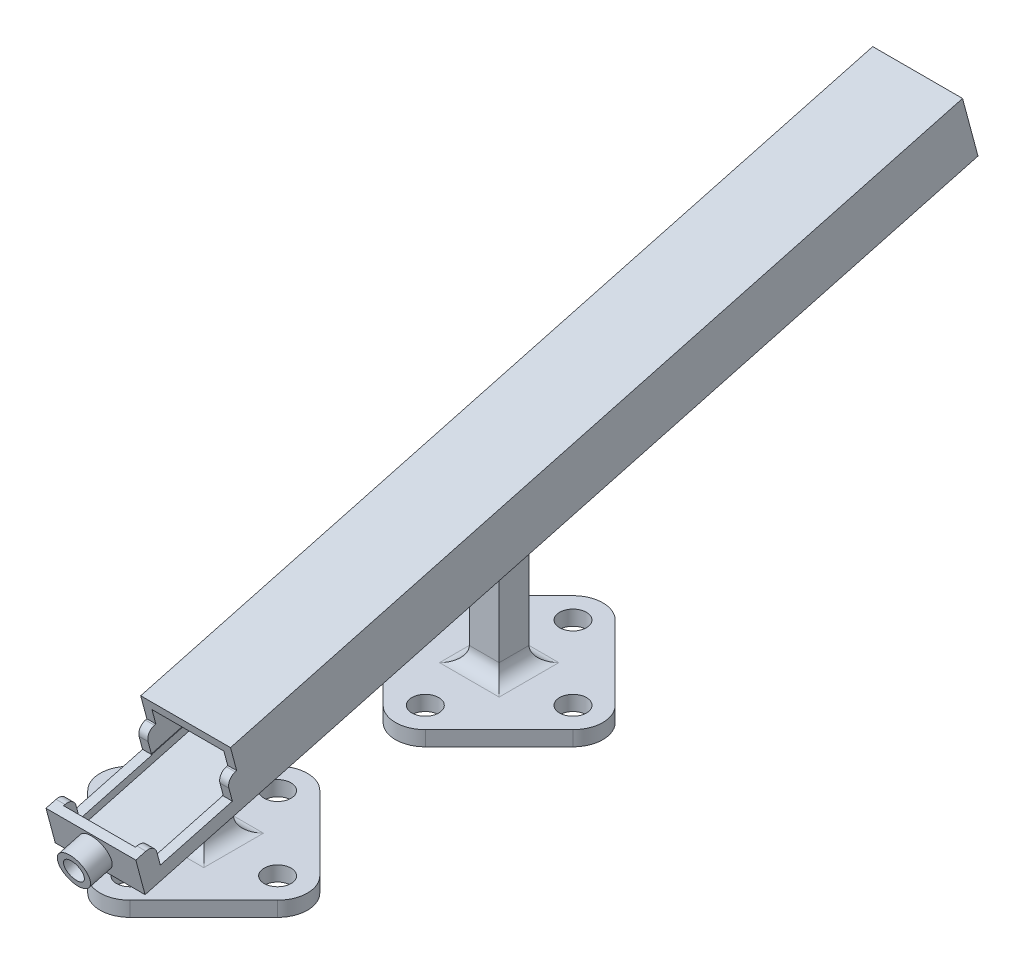
SolidWorks part; units mm, degrees
ref_plane "Front" through (0, 0, 0) normal (0, 0, 1) x (1, 0, 0)
ref_plane "Top" through (0, 0, 0) normal (0, 1, 0) x (1, 0, 0)
ref_plane "Right" through (0, 0, 0) normal (1, 0, 0) x (0, 0, -1)
ref_axis "Axis1" through (0, 55, 0) along (0, -1, 0)
ref_axis "Axis2" through (88.99, 0, 0) along (-1, 0, 0)
ref_axis "Axis3" through (0, 0, 55) along (0, 0, -1)
sketch "Sketch1" plane through (0, 0, 0) normal (0, 1, 0) x (1, 0, 0)
  line L0 (-24.75, 0) -> (0, 24.75) construction
  line L9 (-24.75, 0) -> (0, -24.75) construction
  line L11 (0, 24.75) -> (24.75, 0) construction
  line L12 (0, -24.75) -> (24.75, 0) construction
  line L13 (-24.75, 0) -> (24.75, 0) construction
  line L14 (0, 24.75) -> (0, -24.75) construction
  line L15 (-31.8211, 7.0711) -> (-7.0711, 31.8211)
  line L16 (7.0711, 31.8211) -> (31.8211, 7.0711)
  line L17 (7.0711, -31.8211) -> (31.8211, -7.0711)
  line L18 (-31.8211, -7.0711) -> (-7.0711, -31.8211)
  line L19 (0, -38.8921) -> (38.8921, 0) construction
  line L20 (-38.8921, 0) -> (0, -38.8921) construction
  line L21 (0, 38.8921) -> (38.8921, 0) construction
  line L22 (-38.8921, 0) -> (0, 38.8921) construction
  arc A4 (7.0711, -31.8211) -> (-7.0711, -31.8211) centre (0, -24.75) cw
  arc A5 (31.8211, 7.0711) -> (31.8211, -7.0711) centre (24.75, 0) cw
  arc A6 (-7.0711, 31.8211) -> (7.0711, 31.8211) centre (0, 24.75) cw
  arc A7 (-31.8211, 7.0711) -> (-31.8211, -7.0711) centre (-24.75, 0) ccw
  circle A8 centre (0, 24.75) radius 4.5
  circle A9 centre (24.75, 0) radius 4.5
  circle A10 centre (0, -24.75) radius 4.5
  circle A11 centre (-24.75, 0) radius 4.5
  point P1 (0, 0)
  dimension "D3" = 10
  dimension "D4" = 9
  dimension "D1" = 49.5
  dimension "D2" = 10
extrude "Boss-Extrude1" add sketch "Sketch1" along normal mid plane 5
ref_plane "Plane1" through (0, 0, 49.5) normal (0, 0, 1) x (1, 0, 0)
mirror "Mirror3" about plane through (0, 0, 49.5) normal (0, 0, 1) of bodies 101
sketch "Sketch2" plane through (0, 0, 0) normal (1, 0, 0) x (0, 0, -1)
  line L0 (-106.0711, 2.5) -> (-130.8211, 2.5) construction
  line L1 (-104, 2.5) -> (-94, 2.5)
  line L2 (-104, 2.5) -> (-104, 47.5)
  line L3 (-104, 47.5) -> (-94, 47.5)
  line L4 (-94, 2.5) -> (-94, 47.5)
  line L5 (-106.0711, -2.5) -> (-91.9289, -2.5) construction
  line L6 (-67.1789, -2.5) -> (-91.9289, -2.5) construction
  point P8 (-99, -2.5)
  point P9 (-99, 47.5)
  dimension "D1" = 10
  dimension "D2" = 50
extrude "Boss-Extrude2" add sketch "Sketch2" along normal mid plane 10 separate body
mirror "Mirror5" about plane through (0, 0, 49.5) normal (0, 0, 1) of bodies 103
sketch "Sketch3" plane through (0, 0, 0) normal (1, 0, 0) x (0, 0, -1)
  line L0 (-104, 17.5) -> (5, 46.7065)
  line L1 (-67.1789, -2.5) -> (-91.9289, -2.5) construction
  line L2 (-104, 47.5) -> (-104, 2.5) construction
  line L3 (-106.0711, 2.5) -> (-130.8211, 2.5) construction
  line L4 (5, 47.5) -> (5, 2.5) construction
  point P6 (-104, 17.5)
  dimension "D1" = 15
  dimension "D2" = 15
extrude "Cut-Extrude1" cut sketch "Sketch3" against normal through all both and the other way through all
sketch "Sketch4" plane through (0, 0, 0) normal (1, 0, 0) x (0, 0, -1)
  line L0 (-130.8211, 10.3133) -> (14.0678, 49.1362)
  line L1 (-130.8211, 10.3133) -> (-131.3387, 12.2452)
  line L2 (14.0678, 49.1362) -> (13.5502, 51.068)
  line L3 (-131.3387, 12.2452) -> (13.5502, 51.068)
  line L6 (-104, 17.5) -> (-94, 20.1795) construction
  dimension "D1" = 2
  dimension "D2" = 150
extrude "Boss-Extrude3" add sketch "Sketch4" along normal mid plane 24.1 separate body
combine bodies "Combine1" operation type add bodies to combine 102 106
combine bodies "Combine2" operation type add bodies to combine 107 101
fillet "Fillet1" radius 5 4 edges at (0, 2.5, 94) (-5, 2.5, 99) (0, 2.5, 104) (5, 2.5, 99)
fillet "Fillet2" radius 5 4 edges at (0, 2.5, 5) (0, 2.5, -5) (-5, 2.5, 0) (5, 2.5, 0)
sketch "Sketch5" plane through (0, 44.2596, 11.8593) normal (0, 0.9659, 0.2588) x (1, 0, 0)
  line L0 (12.05, -111.6442) -> (0, -111.6442) construction
  line L1 (12.05, 26.3058) -> (12.05, -123.6942) construction
  line L2 (0, -111.6442) -> (0, -123.6942) construction
  line L3 (12.05, -123.6942) -> (-12.05, -123.6942) construction
  line L4 (-11.83, -111.6442) -> (-12.05, -123.6942)
  line L5 (-12.05, -123.6942) -> (0, -123.6942)
  line L6 (0, -123.6942) -> (12.05, -123.6942)
  line L7 (12.05, -123.6942) -> (12.05, -111.6442)
  circle A0 centre (0, -111.6442) radius 8.73 construction
  circle A1 centre (0, -111.6442) radius 8.83
  circle A2 centre (0, -111.6442) radius 11.83
  dimension "D1" = 17.46
  dimension "D2" = 0.1
  dimension "D3" = 3
sketch "Sketch6" plane through (0, 44.2596, 11.8593) normal (0, 0.9659, 0.2588) x (1, 0, 0)
  line L4 (-12.05, 26.3058) -> (-12.05, -123.6942)
  line L5 (-12.05, -123.6942) -> (12.05, -123.6942)
  line L6 (12.05, -123.6942) -> (12.05, 26.3058)
  line L7 (12.05, 26.3058) -> (-12.05, 26.3058)
  line L8 (-12.05, 26.3058) -> (-12.05, -123.6942)
  line L9 (-12.05, -123.6942) -> (12.05, -123.6942)
  line L10 (12.05, -123.6942) -> (12.05, 26.3058)
  line L11 (12.05, 26.3058) -> (-12.05, 26.3058)
  line L16 (-15.05, 29.3058) -> (-15.05, -126.6942)
  line L17 (-15.05, -126.6942) -> (15.05, -126.6942)
  line L18 (15.05, -126.6942) -> (15.05, 29.3058)
  line L19 (15.05, 29.3058) -> (-15.05, 29.3058)
  line L20 (-15.05, 29.3058) -> (-15.05, -126.6942)
  line L21 (-15.05, -126.6942) -> (15.05, -126.6942)
  line L22 (15.05, -126.6942) -> (15.05, 29.3058)
  line L23 (15.05, 29.3058) -> (-15.05, 29.3058)
  dimension "D1" = 0
  dimension "D2" = 3
extrude "Boss-Extrude4" add sketch "Sketch6" against normal up to vertex (2 mm away) and the other way blind 10 up to point (12.05, 49.1362, -14.0678)
sketch "Sketch7" plane through (0, 53.9188, 14.4475) normal (0, 0.9659, 0.2588) x (1, 0, 0)
  line L0 (12.05, 26.3058) -> (12.05, -123.6942) construction
  line L1 (12.05, 26.3058) -> (12.05, -91.6942)
  line L3 (-12.05, 26.3058) -> (-12.05, -123.6942) construction
  line L4 (15.05, 29.3058) -> (-15.05, 29.3058)
  line L5 (-15.05, 29.3058) -> (-15.05, -126.6942)
  line L6 (-15.05, -126.6942) -> (15.05, -126.6942)
  line L7 (15.05, -126.6942) -> (15.05, 29.3058)
  line L8 (15.05, 29.3058) -> (-15.05, 29.3058)
  line L9 (-15.05, 29.3058) -> (-15.05, -91.6942)
  line L11 (15.05, -91.6942) -> (15.05, 29.3058)
  line L12 (12.05, 26.3058) -> (-12.05, 26.3058) construction
  line L14 (-12.05, 26.3058) -> (-12.05, -91.6942)
  line L15 (12.05, 26.3058) -> (-12.05, 26.3058)
  line L16 (15.05, -91.6942) -> (12.05, -91.6942)
  line L17 (-12.05, -91.6942) -> (-15.05, -91.6942)
  line L18 (-15.05, -126.6942) -> (15.05, -126.6942) construction
  dimension "D2" = 35
  dimension "D1" = 0
extrude "Boss-Extrude5" add sketch "Sketch7" along normal blind 5
sketch "Sketch8" plane through (0, 58.7485, 15.7416) normal (0, 0.9659, 0.2588) x (1, 0, 0)
  line L0 (-15.05, 29.3058) -> (-15.05, -91.6942) construction
  line L1 (-15.05, -91.6942) -> (15.05, -91.6942)
  line L2 (-15.05, -91.6942) -> (-15.05, 29.3058)
  line L3 (-15.05, 29.3058) -> (15.05, 29.3058)
  line L4 (15.05, -91.6942) -> (15.05, 29.3058)
extrude "Boss-Extrude6" add sketch "Sketch8" along normal blind 3
sketch "Sketch10" plane through (0, 6.8085, -25.4095) normal (0, -0.2588, 0.9659) x (1, 0, 0)
  line L4 (-12.05, 45.8209) -> (12.05, 45.8209)
  line L5 (12.05, 45.8209) -> (12.05, 60.8209)
  line L6 (12.05, 60.8209) -> (-12.05, 60.8209)
  line L7 (-12.05, 60.8209) -> (-12.05, 45.8209)
  line L8 (-12.05, 45.8209) -> (12.05, 45.8209)
  line L9 (12.05, 45.8209) -> (12.05, 60.8209)
  line L10 (12.05, 60.8209) -> (-12.05, 60.8209)
  line L11 (-12.05, 60.8209) -> (-12.05, 45.8209)
  dimension "D1" = 0
extrude "Cut-Extrude2" cut sketch "Sketch10" against normal up to next
sketch "Sketch11" plane through (0, 7.5849, -28.3073) normal (0, 0.2588, -0.9659) x (-1, 0, 0)
  line L0 (-12.05, 45.8209) -> (-11.85, 45.8209)
  line L1 (-12.05, 45.8209) -> (12.05, 45.8209) construction
  line L2 (-11.85, 45.8209) -> (-11.85, 48.5209)
  line L3 (-11.85, 48.5209) -> (-12.05, 48.5209)
  line L4 (-12.05, 60.8209) -> (-12.05, 45.8209) construction
  line L5 (-12.05, 48.5209) -> (-12.05, 45.8209)
  line L6 (0, 43.8209) -> (0, 45.8209) construction
  line L7 (-15.05, 43.8209) -> (15.05, 43.8209) construction
  line L8 (12.05, 48.5209) -> (12.05, 45.8209)
  line L9 (11.85, 48.5209) -> (12.05, 48.5209)
  line L10 (11.85, 45.8209) -> (11.85, 48.5209)
  line L11 (12.05, 45.8209) -> (11.85, 45.8209)
  dimension "D1" = 0.2
  dimension "D2" = 2.7
extrude "Boss-Extrude7" add sketch "Sketch11" against normal up to surface (153 mm away) up to face at (0, 17.0748, 132.6328)
sketch "Sketch12" plane through (0, 53.9188, 14.4475) normal (0, 0.9659, 0.2588) x (1, 0, 0)
  line L0 (-15.05, -91.6942) -> (-15.05, -126.6942) construction
  line L1 (-15.05, -95.1942) -> (-11.85, -95.1942)
  line L2 (-15.05, -95.1942) -> (-15.05, -120.1942)
  line L3 (-15.05, -120.1942) -> (-11.85, -120.1942)
  line L4 (-11.85, -95.1942) -> (-11.85, -120.1942)
  line L5 (-11.85, -123.6942) -> (-11.85, 29.3058) construction
  line L6 (-13.55, -91.6942) -> (-13.55, -95.1942) construction
  line L7 (-15.05, -91.6942) -> (-12.05, -91.6942) construction
  line L8 (-11.85, -120.1942) -> (-11.85, -123.6942) construction
  line L9 (-12.05, -123.6942) -> (12.05, -123.6942) construction
  line L10 (0, -91.6942) -> (0, -126.6942) construction
  line L11 (-15.05, -91.6942) -> (15.05, -91.6942) construction
  line L12 (-15.05, -126.6942) -> (15.05, -126.6942) construction
  line L13 (11.85, -120.1942) -> (11.85, -123.6942) construction
  line L14 (13.55, -91.6942) -> (13.55, -95.1942) construction
  line L15 (11.85, -95.1942) -> (11.85, -120.1942)
  line L16 (15.05, -120.1942) -> (11.85, -120.1942)
  line L17 (15.05, -95.1942) -> (15.05, -120.1942)
  line L18 (15.05, -95.1942) -> (11.85, -95.1942)
  dimension "D1" = 25
extrude "Cut-Extrude3" cut sketch "Sketch12" against normal blind 7.5
sketch "Sketch13" plane through (0, -32.7909, 122.3772) normal (0, -0.2588, 0.9659) x (1, 0, 0)
  line L0 (-15.05, 55.8209) -> (15.05, 55.8209) construction
  line L1 (-15.05, 55.8209) -> (-15.05, 43.8209) construction
  circle A0 centre (0, 49.8209) radius 3.4
  circle A1 centre (0, 49.8209) radius 5.4
  point P4 (0, 55.8209)
  point P7 (-15.05, 49.8209)
  dimension "D1" = 6.8
  dimension "D2" = 2
extrude "Boss-Extrude8" add sketch "Sketch13" along normal blind 7.5
sketch "Sketch14" plane through (0, -32.7909, 122.3772) normal (0, -0.2588, 0.9659) x (1, 0, 0)
  circle A0 centre (0, 49.8209) radius 3.4
  circle A1 centre (0, 49.8209) radius 3.4 construction
extrude "Cut-Extrude4" cut sketch "Sketch14" against normal up to next
fillet "Fillet3" radius 3 4 edges at (-13.55, 29.2808, 106.398) (13.55, 29.2808, 106.398) (13.55, 22.8103, 130.5462) (-13.55, 22.8103, 130.5462)
sketch "Sketch15" plane through (0, 7.5849, -28.3073) normal (0, 0.2588, -0.9659) x (-1, 0, 0)
  line L4 (-15.05, 63.8209) -> (-15.05, 43.8209)
  line L5 (-15.05, 43.8209) -> (15.05, 43.8209)
  line L6 (15.05, 43.8209) -> (15.05, 63.8209)
  line L7 (15.05, 63.8209) -> (-15.05, 63.8209)
  line L8 (-15.05, 63.8209) -> (-15.05, 43.8209)
  line L9 (-15.05, 43.8209) -> (15.05, 43.8209)
  line L10 (15.05, 43.8209) -> (15.05, 63.8209)
  line L11 (15.05, 63.8209) -> (-15.05, 63.8209)
  line L16 (12.05, 48.5209) -> (12.05, 60.8209)
  line L17 (11.85, 48.5209) -> (12.05, 48.5209)
  line L18 (11.85, 45.8209) -> (11.85, 48.5209)
  line L19 (-11.85, 45.8209) -> (11.85, 45.8209)
  line L20 (-11.85, 48.5209) -> (-11.85, 45.8209)
  line L21 (-12.05, 48.5209) -> (-11.85, 48.5209)
  line L22 (-12.05, 60.8209) -> (-12.05, 48.5209)
  line L23 (12.05, 60.8209) -> (-12.05, 60.8209)
  line L24 (12.05, 48.5209) -> (12.05, 60.8209)
  line L25 (11.85, 48.5209) -> (12.05, 48.5209)
  line L26 (11.85, 45.8209) -> (11.85, 48.5209)
  line L27 (-11.85, 45.8209) -> (11.85, 45.8209)
  line L28 (-11.85, 48.5209) -> (-11.85, 45.8209)
  line L29 (-12.05, 48.5209) -> (-11.85, 48.5209)
  line L30 (-12.05, 60.8209) -> (-12.05, 48.5209)
  line L31 (12.05, 60.8209) -> (-12.05, 60.8209)
  dimension "D1" = 0
  dimension "D2" = 0
extrude "Boss-Extrude9" add sketch "Sketch15" along normal blind 133
